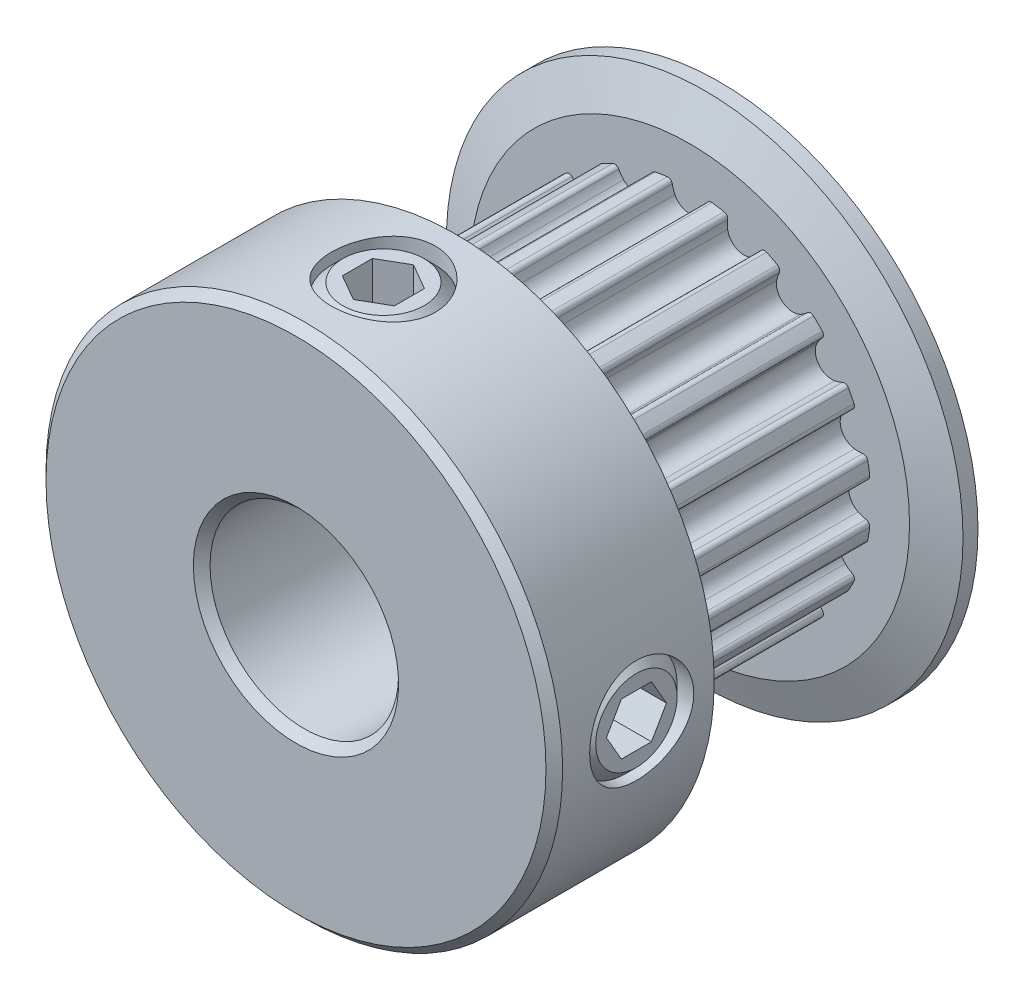
SolidWorks part; units mm, degrees
ref_plane "Front Plane" through (0, 0, 0) normal (0, 0, 1) x (1, 0, 0)
ref_plane "Top Plane" through (0, 0, 0) normal (0, 1, 0) x (1, 0, 0)
ref_plane "Right Plane" through (0, 0, 0) normal (1, 0, 0) x (0, 0, -1)
sketch "Sketch1" plane through (0, 0, 0) normal (0, 0, 1) x (1, 0, 0)
  line L1 (-1.7499, 5.3585) -> (1.7499, 5.3585) construction
  line L4 (0, 0) -> (0, 5.3585) construction
  line L5 (0, 5.3585) -> (0, 11.2095) construction
  line L6 (0, 6.3625) -> (1.9751, 6.0482) construction
  line L7 (1.9751, 6.0482) -> (2.6648, 5.8229) construction
  line L8 (1.9751, 6.0482) -> (1.7499, 5.3585) construction
  line L9 (-1.9751, 6.0482) -> (-1.7499, 5.3585) construction
  line L10 (-1.8963, 5.8067) -> (-2.841, 8.6995)
  line L11 (-2.841, 8.6995) -> (2.841, 8.6995)
  line L12 (2.841, 8.6995) -> (1.8963, 5.8067)
  circle A0 centre (0, 0) radius 6.3625 construction
  circle A1 centre (0, 0) radius 8.6995 construction
  circle A2 centre (0, 0) radius 6.1085 construction
  arc A3 (-0.4989, 5.6703) -> (0.4989, 5.6703) centre (0, 5.9135) ccw
  arc A4 (-0.4989, 5.6703) -> (-0.5855, 5.9387) centre (0.4, 6.1085) cw
  arc A5 (-1.8963, 5.8067) -> (-0.7518, 6.0621) centre (0, 0) cw
  arc A6 (-0.5855, 5.9387) -> (-0.7518, 6.0621) centre (-0.7333, 5.9132) ccw
  arc A7 (1.8963, 5.8067) -> (0.7518, 6.0621) centre (0, 0) ccw
  arc A8 (0.5855, 5.9387) -> (0.7518, 6.0621) centre (0.7333, 5.9132) cw
  arc A9 (0.4989, 5.6703) -> (0.5855, 5.9387) centre (-0.4, 6.1085) ccw
  point P6 (0, 20.9083)
  point P11 (0, 6.3625)
  point P13 (0, 8.6995)
  point P14 (0, 6.1085)
  dimension "D1" = 9.6989
  dimension "D2" = 4.847
sketch "Sketch2" plane through (0, 0, 0) normal (1, 0, 0) x (0, 0, -1)
  line L0 (-7.135, 3.175) -> (7.135, 3.175)
  line L1 (-7.135, 3.175) -> (-7.135, 8.6995)
  line L2 (-1.75, 8.6995) -> (-7.135, 8.6995)
  line L3 (-2.255, 3.175) -> (-2.255, 8.6995) construction
  line L4 (-2.255, 8.6995) -> (-1.245, 8.6995) construction
  line L5 (-1.245, 8.6995) -> (-1.245, 6.1085) construction
  line L6 (-1.245, 6.1085) -> (6.125, 6.1085)
  line L7 (6.125, 6.1085) -> (6.125, 8.6995) construction
  line L8 (6.125, 8.6995) -> (7.135, 8.6995) construction
  line L9 (7.135, 8.6995) -> (7.135, 3.175)
  line L10 (-7.135, 0) -> (7.135, 0) construction
  line L11 (6.63, 8.6995) -> (6.125, 7.404)
  line L12 (-1.245, 7.404) -> (-1.75, 8.6995)
  line L14 (-1.245, 7.404) -> (-1.245, 6.1085)
  line L15 (6.125, 6.1085) -> (6.125, 7.404)
  line L16 (6.63, 8.6995) -> (7.135, 8.6995)
  arc A0 (-1.245, 7.404) -> (-1.75, 8.6995) centre (-3.1592, 7.404) ccw construction
  arc A1 (6.125, 7.404) -> (6.63, 8.6995) centre (8.0392, 7.404) cw construction
  point P12 (-1.245, 7.404)
  point P14 (-1.75, 8.6995)
  point P20 (6.125, 7.404)
  point P21 (6.63, 8.6995)
  point P25 (6.125, 0)
  point P26 (-1.245, 0)
  dimension "OA" = 14.27
  dimension "Bore" = 6.35
  dimension "Outside Width" = 8.38
  dimension "Inside Width" = 7.37
revolve "Revolve1" add sketch "Sketch2" angle 360 mid plane about L10
sketch "Sketch3" plane through (0, 0, 0) normal (0, 0, 1) x (1, 0, 0)
  line L6 (2.841, 8.6995) -> (-2.841, 8.6995)
  line L7 (1.8963, 5.8067) -> (2.841, 8.6995)
  line L8 (-2.841, 8.6995) -> (-1.8963, 5.8067)
  line L9 (2.841, 8.6995) -> (-2.841, 8.6995)
  line L10 (1.8963, 5.8067) -> (2.841, 8.6995)
  line L11 (-2.841, 8.6995) -> (-1.8963, 5.8067)
  arc A8 (1.8963, 5.8067) -> (0.7518, 6.0621) centre (0, 0) ccw
  arc A9 (0.7518, 6.0621) -> (0.5855, 5.9387) centre (0.7333, 5.9132) ccw
  arc A10 (0.4989, 5.6703) -> (0.5855, 5.9387) centre (-0.4, 6.1085) ccw
  arc A11 (-0.4989, 5.6703) -> (0.4989, 5.6703) centre (0, 5.9135) ccw
  arc A12 (-0.5855, 5.9387) -> (-0.4989, 5.6703) centre (0.4, 6.1085) ccw
  arc A13 (-0.5855, 5.9387) -> (-0.7518, 6.0621) centre (-0.7333, 5.9132) ccw
  arc A14 (-0.7518, 6.0621) -> (-1.8963, 5.8067) centre (0, 0) ccw
  arc A15 (1.8963, 5.8067) -> (0.7518, 6.0621) centre (0, 0) ccw
  arc A16 (0.7518, 6.0621) -> (0.5855, 5.9387) centre (0.7333, 5.9132) ccw
  arc A17 (0.4989, 5.6703) -> (0.5855, 5.9387) centre (-0.4, 6.1085) ccw
  arc A18 (-0.4989, 5.6703) -> (0.4989, 5.6703) centre (0, 5.9135) ccw
  arc A19 (-0.5855, 5.9387) -> (-0.4989, 5.6703) centre (0.4, 6.1085) ccw
  arc A20 (-0.5855, 5.9387) -> (-0.7518, 6.0621) centre (-0.7333, 5.9132) ccw
  arc A21 (-0.7518, 6.0621) -> (-1.8963, 5.8067) centre (0, 0) ccw
  dimension "D1" = 0
extrude "Cut-Extrude1" cut sketch "Sketch3" against normal up to vertex (6.125 mm away) from vertex up to point (0, 6.1085, -6.125) starting at point (0, 6.1085, 1.245)
pattern_circular "CirPattern1" count 20 over 360 about axis through (0, 0, 7.135) along (0, 0, 1) of "Cut-Extrude1"
sketch "Sketch4" plane through (0, 0, 0) normal (1, 0, 0) x (0, -1, 0)
  line L0 (0, -1.245) -> (0, -7.135) construction
  line L1 (-3.175, -7.135) -> (3.175, -7.135) construction
  line L2 (7.404, -1.245) -> (-7.404, -1.245) construction
  circle A0 centre (0, -4.19) radius 1.7526
extrude "Cut-Extrude2" cut sketch "Sketch4" along normal through all
ref_plane "Plane1" through (0, 0, 4.19) normal (0, 0, 1) x (1, 0, 0)
sketch "Sketch5" plane through (0, 0, 4.19) normal (0, 0, 1) x (1, 0, 0)
  line L0 (0, 0) -> (0, 8.6995) construction
  line L1 (3.175, -1.3716) -> (3.175, 0)
  line L2 (3.556, -1.7526) -> (8.1401, -1.7526)
  line L3 (3.175, 0) -> (8.6995, 0) construction
  line L4 (3.175, 0) -> (8.5211, 0)
  line L5 (8.5211, 0) -> (8.5211, -1.3716)
  line L6 (3.556, -1.7526) -> (3.175, -1.3716)
  line L7 (8.5211, -1.3716) -> (8.1401, -1.7526)
  circle A0 centre (0, 0) radius 8.6995 construction
  circle A1 centre (0, 0) radius 3.175 construction
  point P2 (3.175, -1.7526)
  point P11 (8.5211, -1.7526)
revolve "Revolve2" add sketch "Sketch5" angle 360 mid plane about L4
sketch "Sketch6" plane through (8.5211, 5.3841, 0) normal (-1, 0, 0) x (0, -1, 0)
  line L1 (5.3841, 5.2019) -> (4.5078, 4.6959)
  line L2 (4.5078, 4.6959) -> (4.5078, 3.6841)
  line L3 (4.5078, 3.6841) -> (5.3841, 3.1781)
  line L4 (5.3841, 3.1781) -> (6.2604, 3.6841)
  line L5 (6.2604, 3.6841) -> (6.2604, 4.6959)
  line L6 (6.2604, 4.6959) -> (5.3841, 5.2019)
  circle A0 centre (5.3841, 4.19) radius 0.8763 construction
  dimension "D1" = 1.7526
extrude "Cut-Extrude3" cut sketch "Sketch6" along normal blind 1.3144
pattern_circular "CirPattern3" count 2 over 90 about axis through (0, 0, 7.135) along (0, 0, 1) of "Cut-Extrude2", "Revolve2", "Cut-Extrude3"
chamfer "Chamfer1" distance 0.2807 angle 45 2 edges at (3.175, 0, 7.135) (8.6995, 0, 7.135)
ref_axis "Center Axis 1" through (0, 0, -7.135) along (0, 0, 1)
ref_plane "Contact Plane 1" through (0, 0, 7.135) normal (0, 0, 1) x (1, 0, 0)
ref_plane "Contact Plane 2" through (0, 0, -7.135) normal (0, 0, -1) x (-1, 0, 0)
equation "\"D2@Sketch1\"= \"D1@Sketch1\" / 2"
equation "\"D1@Sketch6\" = \"Set Screw@Sketch4\" / 2"
equation "\"D1@Cut-Extrude3\" = \"D1@Sketch6\"*.75"
